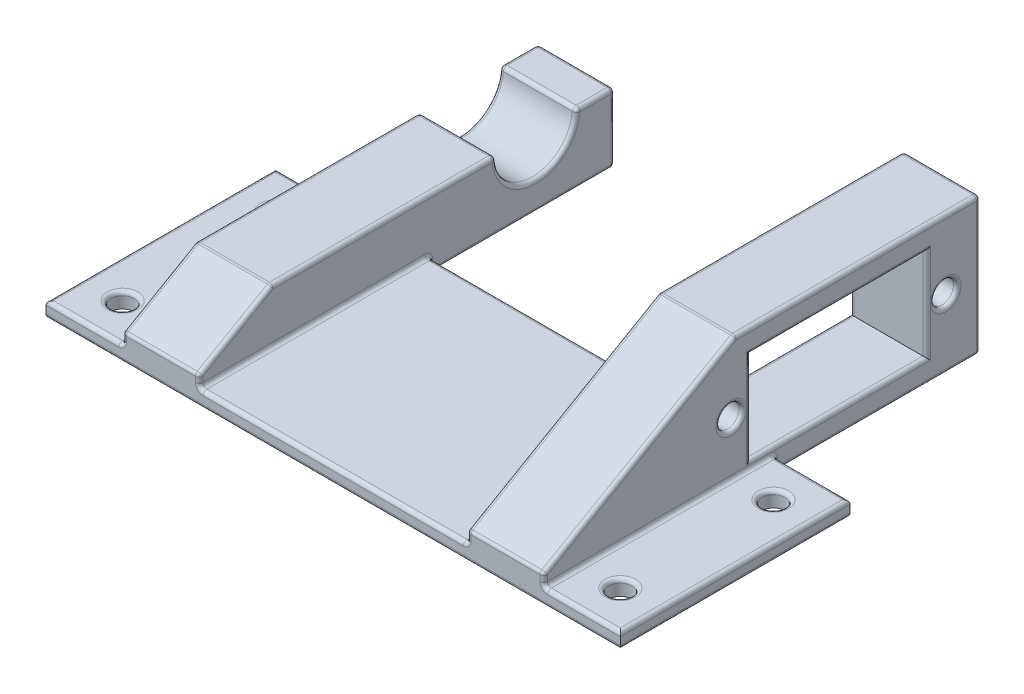
SolidWorks part; units mm, degrees
ref_plane "Front Plane" through (0, 0, 0) normal (0, 0, 1) x (1, 0, 0)
ref_plane "Top Plane" through (0, 0, 0) normal (0, 1, 0) x (1, 0, 0)
ref_plane "Right Plane" through (0, 0, 0) normal (1, 0, 0) x (0, 0, -1)
sketch "Sketch4" plane through (0, 0, 0) normal (0, 1, 0) x (1, 0, 0)
  line L1 (-37.5, -15) -> (37.5, -15)
  line L2 (-37.5, -15) -> (-37.5, 15)
  line L3 (-37.5, 15) -> (37.5, 15)
  line L4 (37.5, -15) -> (37.5, 15)
  line L5 (-37.5, -15) -> (37.5, 15) construction
  line L6 (-37.5, 15) -> (37.5, -15) construction
  point P0 (0, 0)
  dimension "D1" = 30
  dimension "D2" = 75
extrude "Boss-Extrude3" add sketch "Sketch4" along normal blind 2
ref_plane "Plane2" through (22.5, 0, 0) normal (1, 0, 0) x (0, 0, -1)
sketch "Sketch5" plane through (22.5, 0, 0) normal (1, 0, 0) x (0, 0, -1)
  line L0 (15, 2) -> (15, 0) construction
  line L1 (42, 18) -> (-15, 18)
  line L2 (42, 18) -> (42, 0)
  line L3 (42, 0) -> (-15, 0)
  line L4 (-15, 18) -> (-15, 0)
  line L5 (42, 18) -> (-15, 0) construction
  line L6 (42, 0) -> (-15, 18) construction
  point P0 (13.5, 9)
  dimension "D1" = 18
  dimension "D2" = 27
extrude "Boss-Extrude4" add sketch "Sketch5" along normal mid plane 10
sketch "Sketch6" plane through (27.5, 0, 0) normal (1, 0, 0) x (0, 0, -1)
  line L0 (42, 0) -> (42, 18) construction
  line L1 (12, 3) -> (35, 3)
  line L2 (12, 3) -> (12, 15)
  line L3 (12, 15) -> (35, 15)
  line L4 (35, 3) -> (35, 15)
  line L5 (12, 3) -> (35, 15) construction
  line L6 (12, 15) -> (35, 3) construction
  point P0 (23.5, 9)
  point P10 (42, 9)
  dimension "D1" = 7
  dimension "D2" = 12
  dimension "D3" = 23
extrude "Cut-Extrude2" cut sketch "Sketch6" against normal through all both and the other way through all
ref_plane "Plane3" through (-17.5, 0, 0) normal (-1, 0, 0) x (0, 0, 1)
sketch "Sketch7" plane through (-17.5, 0, 0) normal (-1, 0, 0) x (0, 0, 1)
  line L0 (-23.75, 9) -> (15, 9)
  line L1 (-39.25, 9) -> (-34.25, 9)
  line L2 (-39.25, 9) -> (-39.25, 0)
  line L3 (-39.25, 0) -> (15, 0)
  line L4 (15, 9) -> (15, 0)
  line L5 (-39.25, 9) -> (15, 0) construction
  line L6 (-39.25, 0) -> (15, 9) construction
  line L7 (-35, 15) -> (-35, 3) construction
  arc A0 (-34.25, 9) -> (-23.75, 9) centre (-29, 9) ccw
  circle A1 centre (-29, 9) radius 5 construction
  point P0 (-12.125, 4.5)
  point P15 (-35, 9)
  dimension "D2" = 10.5
  dimension "D1" = 5
extrude "Boss-Extrude5" add sketch "Sketch7" along normal blind 10
sketch "Sketch8" plane through (0, 2, 0) normal (0, 1, 0) x (1, 0, 0)
  line L0 (37.5, 15) -> (27.5, 15) construction
  line L1 (-27.5, 15) -> (-37.5, 15) construction
  line L2 (27.5, -15) -> (37.5, -15) construction
  circle A0 centre (-32.5, 10) radius 1.5
  circle A1 centre (-32.5, -10) radius 1.5
  circle A2 centre (32.5, 10) radius 1.5
  circle A3 centre (32.5, -10) radius 1.5
  point P11 (32.5, 15)
  point P16 (-32.5, 15)
  dimension "D1" = 3
  dimension "D2" = 5
  dimension "D3" = 5
extrude "Cut-Extrude3" cut sketch "Sketch8" against normal through all
sketch "Sketch9" plane through (17.5, 0, 0) normal (-1, 0, 0) x (0, 0, 1)
  circle A0 centre (-9.5, 9) radius 1.5
  circle A1 centre (-37.5, 9) radius 1.5
  dimension "D1" = 3
extrude "Cut-Extrude4" cut sketch "Sketch9" against normal through all
ref_axis "Axis1" through (-41.2377, 9, -29) along (1, 0, 0)
chamfer "Chamfer1" distance 25 angle 30 1 edges at (22.5, 18, 15) first distance on face at (22.5, 18, -13.5)
chamfer "Chamfer2" distance 5.5 angle 60 1 edges at (-22.5, 9, 15) first distance on face at (0, 3.0944, 15)
fillet "Fillet1" radius 0.5 72 edges at (-37.5, 0, 0) (0, 0, 15) (37.5, 0, 0) (32.5, 0, -15) (0, 0, -15) (-32.5, 0, -15) (-22.5, 3.5, 15) (-22.5, 9, -23.75) (-22.5, 9, 5.4737) (-22.5, 9, -34.25) (-27.5, 1, -15) (-27.5, 0, -27.125) (-27.5, 9, -36.75) (-27.5, 3.75, -29) (-27.5, 9, -9.1381) (-27.5, 6.25, 10.2369) (-27.5, 2.75, 15) (-17.5, 3.75, -29) (-17.5, 9, -36.75) (-17.5, 0, -27.125) (-17.5, 1, -15) (-17.5, 2.75, 15) (-17.5, 6.25, 10.2369) (-17.5, 9, -9.1381) (17.5, 1, -15) (17.5, 0, -28.5) (17.5, 2.7831, 15) (17.5, 3, -23.5) (17.5, 9, -12) (17.5, 15, -23.5) (17.5, 9, -35) (27.5, 0, -28.5) (27.5, 1, -15) (27.5, 2.7831, 15) (27.5, 9, -12) (27.5, 3, -23.5) (27.5, 9, -35) (27.5, 15, -23.5) (22.5, 3.5662, 15) (17.5, 10.7831, 2.5) (27.5, 10.7831, 2.5) (27.5, 18, -26) (22.5, 18, -10) (17.5, 18, -26) (-22.5, 9, -39.25) (-27.5, 4.5, -39.25) (-22.5, 0, -39.25) (-17.5, 4.5, -39.25) (22.5, 0, -42) (27.5, 9, -42) (22.5, 18, -42) (17.5, 9, -42) (32.5, 2, -15) (37.5, 2, 0) (32.5, 2, 15) (27.5, 2, 0) (-37.5, 2, 0) (-32.5, 2, -15) (-27.5, 2, 0) (-32.5, 2, 15) (0, 2, -15) (17.5, 2, 0) (0, 2, 15) (-17.5, 2, 0) (32.5, 2, 11.5) (32.5, 2, -8.5) (-32.5, 2, -8.5) (-32.5, 2, 11.5) (17.5, 9, -36) (17.5, 9, -8) (27.5, 9, -36) (27.5, 9, -8)
